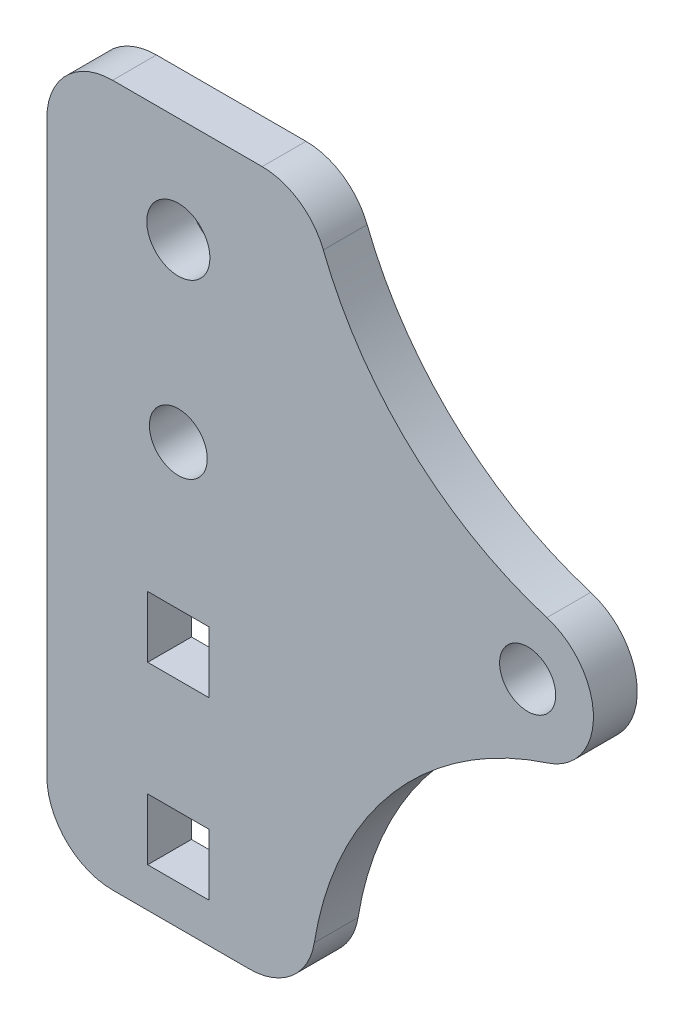
SolidWorks part; units mm, degrees
ref_plane "Front Plane" through (0, 0, 0) normal (0, 0, 1) x (1, 0, 0)
ref_plane "Top Plane" through (0, 0, 0) normal (0, 1, 0) x (1, 0, 0)
ref_plane "Right Plane" through (0, 0, 0) normal (1, 0, 0) x (0, 0, -1)
sketch "Sketch1" plane through (0, 0, 0) normal (0, 0, 1) x (1, 0, 0)
  line L0 (0, 0) -> (0, -25.4) construction
  line L1 (9.525, -30.48) -> (9.525, -33.0089) construction
  line L2 (0, 0) -> (25.3033, -2.2138) construction
  line L6 (-9.525, -30.48) -> (-9.525, 20.32)
  line L13 (-9.525, 20.32) -> (9.525, 20.32)
  line L15 (-2.2225, -27.6225) -> (2.2225, -27.6225)
  line L16 (-2.2225, -27.6225) -> (-2.2225, -23.1775)
  line L17 (-2.2225, -23.1775) -> (2.2225, -23.1775)
  line L18 (2.2225, -27.6225) -> (2.2225, -23.1775)
  line L19 (-2.2225, -27.6225) -> (2.2225, -23.1775) construction
  line L20 (-2.2225, -23.1775) -> (2.2225, -27.6225) construction
  line L21 (0, 12.7) -> (25.3033, -2.2138) construction
  line L22 (-9.525, -30.48) -> (9.525, -30.48)
  line L24 (-2.2225, -14.9225) -> (2.2225, -14.9225)
  line L25 (-2.2225, -14.9225) -> (-2.2225, -10.4775)
  line L26 (-2.2225, -10.4775) -> (2.2225, -10.4775)
  line L27 (2.2225, -14.9225) -> (2.2225, -10.4775)
  line L28 (-2.2225, -14.9225) -> (2.2225, -10.4775) construction
  line L29 (-2.2225, -10.4775) -> (2.2225, -14.9225) construction
  circle A2 centre (25.3033, -2.2138) radius 2.032
  arc A5 (26.7742, -6.7434) -> (26.6969, 2.3403) centre (25.3033, -2.2138) ccw
  circle A9 centre (0, 12.7) radius 2.286
  circle A10 centre (0, 0) radius 2.0955
  arc A13 (9.525, 20.32) -> (26.6969, 2.3403) centre (34.1291, 26.6286) ccw
  arc A14 (9.525, -30.48) -> (26.7742, -6.7434) centre (34.4815, -30.48) cw
  point P4 (0, 0)
  point P16 (0, -30.48)
  point P29 (0, -12.7)
  dimension "D2" = 4.191
  dimension "D6" = 5.08
  dimension "D7" = 12.7
  dimension "D8" = 4.572
  dimension "D10" = 4.064
  dimension "D11" = 25.4
  dimension "D3" = 4.7625
  dimension "D1" = 25.4
  dimension "D4" = 25.4
  dimension "D5" = 85
  dimension "D9" = 4.445
  dimension "D12" = 19.05
  dimension "D13" = 7.62
extrude "Boss-Extrude1" add sketch "Sketch1" along normal blind 3.175
fillet "Fillet1" radius 4.7625 4 edges at (-9.525, -30.48, 1.5875) (9.525, 20.32, 1.5875) (-9.525, 20.32, 1.5875) (9.525, -30.48, 1.5875)
ref_plane "Plane1" through (0, -25.4, 0) normal (0, 1, 0) x (1, 0, 0)
ref_axis "Axis1" through (0, -25.4, -0.1588) along (0, 0, 1)
